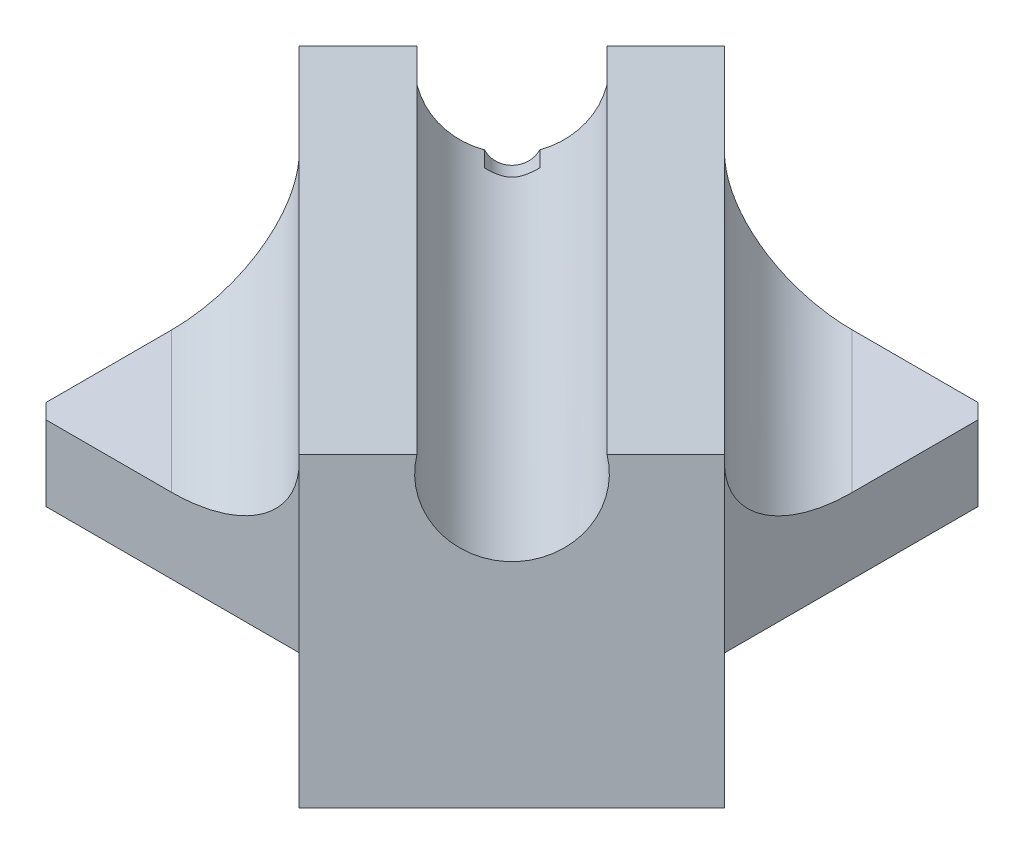
SolidWorks part; units mm, degrees
ref_plane "Front Plane" through (0, 0, 0) normal (0, 0, 1) x (1, 0, 0)
ref_plane "Top Plane" through (0, 0, 0) normal (0, 1, 0) x (1, 0, 0)
ref_plane "Right Plane" through (0, 0, 0) normal (1, 0, 0) x (0, 0, -1)
sketch "Sketch1" plane through (0, 0, 0) normal (0, 1, 0) x (1, 0, 0)
  line L4 (16, -16) -> (-16, -16)
  line L5 (16, -16) -> (16, 16)
  line L6 (16, 16) -> (-16, 16)
  line L7 (-16, -16) -> (-16, 16)
  line L8 (16, -16) -> (-16, 16) construction
  line L9 (16, 16) -> (-16, -16) construction
extrude "Boss-Extrude1" add sketch "Sketch1" along normal blind 5
ref_plane "Plane2" through (0.6046, 0.1508, 0.6046) normal (0.6964, 0.1736, 0.6964) x (0.7071, 0, -0.7071)
sketch "Sketch2" plane through (0.6046, 0.1508, 0.6046) normal (0.6964, 0.1736, 0.6964) x (0.7071, 0, -0.7071)
  line L0 (-4.4695, 14) -> (-10.0081, 14)
  line L1 (4.4695, 14) -> (9.9919, 14)
  line L2 (-10.0081, 14) -> (-10.0081, 2.7327)
  line L3 (-22.6274, 4.924) -> (0, 0.9948) construction
  line L4 (9.9919, 14) -> (9.9919, 2.7299)
  line L5 (0, 0.9948) -> (22.6274, 4.924) construction
  line L6 (9.9919, 2.7299) -> (-10.0081, 2.7327)
  arc A0 (-4.4695, 14) -> (4.4695, 14) centre (0, 13) ccw
  point P2 (-0.0081, 11)
extrude "Boss-Extrude2" add sketch "Sketch2" along normal blind 24 and the other way blind 21
sketch "Sketch3" plane through (-14.019, -3.4958, -14.019) normal (-0.6964, -0.1736, -0.6964) x (-0.6757, -0.1685, 0.7177)
  line L1 (-12.2398, 12.0841) -> (9.393, 12.0841)
  line L2 (-12.2398, 12.0841) -> (-12.2398, 2.7097)
  line L3 (-12.2398, 2.7097) -> (9.393, 2.7097)
  line L4 (9.393, 12.0841) -> (9.393, 2.7097)
extrude "Cut-Extrude1" cut sketch "Sketch3" along normal blind 26
sketch "Sketch4" plane through (-14.019, -3.4958, -14.019) normal (-0.6964, -0.1736, -0.6964) x (-0.6757, -0.1685, 0.7177)
  line L0 (-2.7602, 8.2598) -> (-2.7912, 8.4028)
  line L1 (-2.7912, 8.4028) -> (-0.222, 8.9601)
  line L2 (-0.222, 8.9601) -> (-0.1917, 8.7227)
  arc A0 (-2.7602, 8.2598) -> (-0.1917, 8.7227) centre (-1.5876, 9.1107) ccw
extrude "Cut-Extrude3" cut sketch "Sketch4" against normal blind 3
sketch "Sketch5" plane through (0, 5, 0) normal (0, 1, 0) x (1, 0, 0)
  line L0 (16, -1.8693) -> (1.8464, -16)
  line L1 (1.8464, -16) -> (16, -16)
  line L2 (16, -16) -> (16, -1.8693)
extrude "Boss-Extrude3" add sketch "Sketch5" along normal up to surface up to face at (12.9497, 6.0041, 12.9612)
sketch "Sketch6" plane through (-0.3351, 2.6898, -0.3356) normal (0.1227, -0.9848, 0.1229) x (0.9924, 0.1217, -0.0152)
  line L0 (2.1981, 16.496) -> (10.3181, 24.7414)
  line L1 (10.3181, 24.7414) -> (24.5682, 10.7081)
  line L2 (24.5682, 10.7081) -> (16.4594, 2.474)
  line L3 (16.4594, 2.474) -> (16.4594, 16.7143)
  line L4 (16.4594, 16.7143) -> (2.1981, 16.496)
extrude "Boss-Extrude4" add sketch "Sketch6" along normal up to surface (6.8676 mm away) up to face at (-1.2472, 0, -1.2504)
chamfer "Chamfer2" distance 1 angle 45 1 edges at (-12.8822, 4.7058, -12.8929)
fillet "Fillet3" radius 6 2 edges at (7.0653, 5, -7.0653) (-7.0768, 5, 7.0768)
chamfer "Chamfer3" distance 1 angle 45 2 edges at (16, 2.5, -16) (-16, 2.5, 16)
